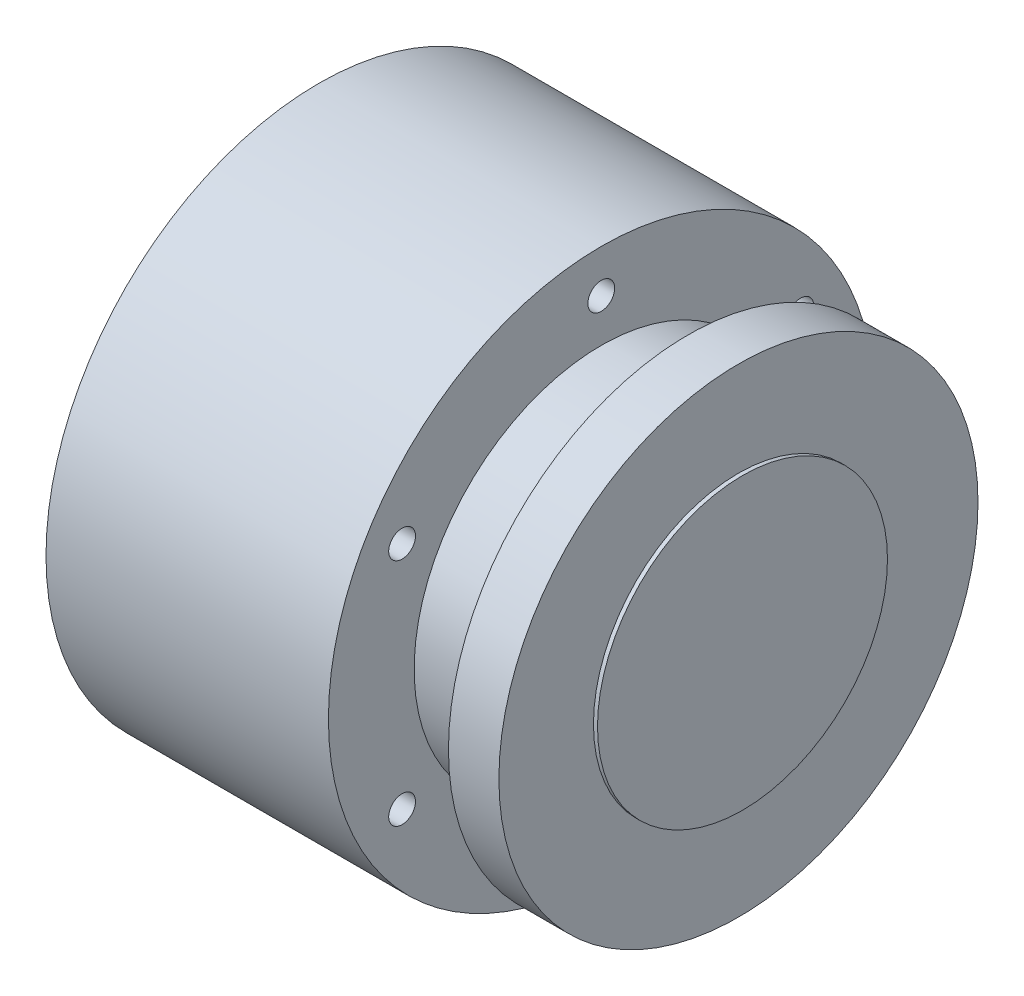
SolidWorks part; units mm, degrees
ref_plane "Front Plane" through (0, 0, 0) normal (1, 0, 0) x (0, 1, 0)
ref_plane "Top Plane" through (0, 0, 0) normal (0, 0, 1) x (0, 1, 0)
ref_plane "Right Plane" through (0, 0, 0) normal (0, 1, 0) x (-1, 0, 0)
sketch "Sketch1" plane through (0, 0, 0) normal (0, 1, 0) x (-1, 0, 0)
  line L0 (0, 68.707) -> (6.35, 68.707)
  line L1 (0, 0) -> (71.12, 0)
  line L2 (0, 0) -> (0, 157.48)
  line L3 (0, 157.48) -> (71.12, 157.48) construction
  line L4 (71.12, 0) -> (71.12, 157.48)
  line L5 (6.35, 68.707) -> (6.35, 149.987)
  line L6 (6.35, 149.987) -> (13.843, 157.48)
  line L7 (63.627, 157.48) -> (71.12, 149.987)
  line L8 (-21.844, 60.325) -> (-21.844, 36.5125)
  line L9 (0, 0) -> (-20.32, 0)
  line L10 (0, 0) -> (0, 47.117)
  line L11 (0, 47.117) -> (-20.32, 47.117)
  line L12 (-20.32, 0) -> (-20.32, 47.117)
  line L13 (71.12, 0) -> (83.82, 0) construction
  line L14 (71.12, 0) -> (71.12, 14.9987) construction
  line L15 (71.12, 14.9987) -> (83.82, 14.9987) construction
  line L16 (83.82, 0) -> (83.82, 14.9987) construction
  line L17 (83.82, 0) -> (96.52, 0) construction
  line L18 (83.82, 0) -> (83.82, 24.13) construction
  line L19 (83.82, 24.13) -> (96.52, 24.13) construction
  line L20 (96.52, 0) -> (96.52, 24.13) construction
  line L21 (-20.32, 0) -> (-35.56, 0)
  line L22 (-20.32, 0) -> (-20.32, 36.5125)
  line L23 (-20.32, 36.5125) -> (-35.56, 36.5125)
  line L24 (-35.56, 0) -> (-35.56, 36.5125)
  line L25 (-21.844, 36.5125) -> (-34.544, 36.5125)
  line L26 (-34.544, 36.5125) -> (-34.544, 60.325)
  line L27 (-34.544, 60.325) -> (-21.844, 60.325)
  line L28 (6.35, 68.707) -> (71.12, 68.707)
  dimension "D1" = 157.48
  dimension "D2" = 71.12
  dimension "D3" = 12.7
  dimension "D4" = 12.7
  dimension "D5" = 14.9987
  dimension "D6" = 24.13
  dimension "D7" = 20.32
  dimension "D8" = 45
  dimension "D9" = 45
  dimension "D10" = 6.35
  dimension "D11" = 47.117
  dimension "D13" = 36.5125
  dimension "D14" = 132.08
  dimension "D12" = 49.784
  dimension "D16" = 60.325
  dimension "D17" = 12.7
  dimension "D18" = 36.5125
  dimension "D19" = 68.707
  dimension "D15" = 1.016
revolve "Revolve1" add sketch "Sketch1" angle 360 about L1 region at (-35.56, 0, 34.3535) region at (10.16, 0, 23.5585) region at (27.94, 0, 18.2562)
revolve "Revolve2" add sketch "Sketch1<3>" angle 360 about L1 region at (28.194, 0, 48.4187)
sketch "Sketch1<3>" plane through (0, 0, 0) normal (0, 1, 0) x (-1, 0, 0) same geometry as "Sketch1"
sketch "Sketch2" plane through (-71.12, 0, 0) normal (-1, 0, 0) x (0, -1, 0)
  line L1 (0, -38.1) -> (36.2353, -11.7735)
  line L2 (36.2353, -11.7735) -> (22.3946, 30.8235)
  line L3 (22.3946, 30.8235) -> (-22.3946, 30.8235)
  line L4 (-22.3946, 30.8235) -> (-36.2353, -11.7735)
  line L5 (-36.2353, -11.7735) -> (0, -38.1)
  circle A0 centre (0, 0) radius 38.1
  circle A1 centre (0, 0) radius 68.707
  circle A3 centre (0, 0) radius 30.8235 construction
  circle A5 centre (0, 0) radius 68.707
  dimension "D2" = 76.2
  dimension "D1" = 0
sketch "Sketch3" plane through (-71.12, 0, 0) normal (-1, 0, 0) x (0, -1, 0)
  circle A0 centre (-22.3946, 30.8235) radius 3.3734
  circle A1 centre (22.3946, 30.8235) radius 3.3734
  circle A2 centre (36.2353, -11.7735) radius 3.3734
  circle A3 centre (0, -38.1) radius 3.3734
  circle A4 centre (-36.2353, -11.7735) radius 3.3734
  point P0 (-36.2353, -11.7735)
  point P2 (0, -38.1)
  point P4 (36.2353, -11.7735)
  point P6 (22.3946, 30.8235)
  point P8 (-22.3946, 30.8235)
  dimension "D1" = 6.7469
extrude "Cut-Extrude1" cut sketch "Sketch3" against normal blind 13.97
sketch "Sketch4" plane through (0, 0, 0) normal (1, 0, 0) x (0, 1, 0)
  line L0 (28.956, -50.1533) -> (57.912, 0)
  line L1 (57.912, 0) -> (28.956, 50.1533)
  line L2 (28.956, 50.1533) -> (-28.956, 50.1533)
  line L3 (-28.956, 50.1533) -> (-57.912, 0)
  line L4 (-57.912, 0) -> (-28.956, -50.1533)
  line L5 (-28.956, -50.1533) -> (28.956, -50.1533)
  circle A0 centre (0, 0) radius 50.1533 construction
  circle A1 centre (0, 0) radius 68.707
  circle A2 centre (0, 0) radius 68.707
  circle A3 centre (28.956, 50.1533) radius 3.3734
  point P11 (0, 0)
  point P12 (0, 0)
  dimension "D3" = 6.7469
  dimension "D2" = 115.824
  dimension "D1" = 0
sketch "Sketch5" plane through (0, 0, 0) normal (1, 0, 0) x (0, 1, 0)
  circle A0 centre (28.956, 50.1533) radius 3.3734 construction
  circle A1 centre (28.956, 50.1533) radius 3.3734
  circle A2 centre (-28.956, 50.1533) radius 3.3734
  circle A3 centre (-57.912, 0) radius 3.3734
  circle A4 centre (-28.956, -50.1533) radius 3.3734
  circle A5 centre (28.956, -50.1533) radius 3.3734
  circle A6 centre (57.912, 0) radius 3.3734
  point P0 (28.956, -50.1533)
  point P2 (57.912, 0)
  point P4 (28.956, 50.1533)
  point P9 (-28.956, -50.1533)
  point P11 (-57.912, 0)
  point P13 (-28.956, 50.1533)
extrude "Cut-Extrude2" cut sketch "Sketch5" against normal blind 13.97
ref_plane "Plane1" through (-35.56, 0, 0) normal (-1, 0, 0) x (0, 0, 1)
equation "\"D9@Sketch1\"=\"D8@Sketch1\""
